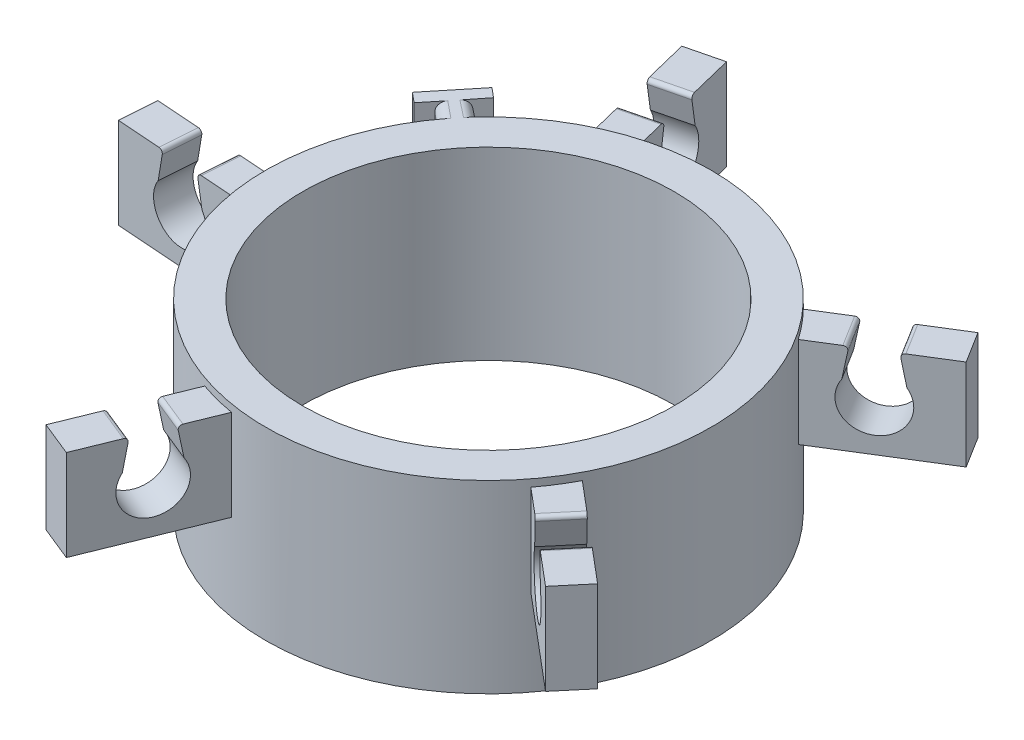
SolidWorks part; units mm, degrees
ref_plane "Plan de face" through (0, 0, 0) normal (0, 0, 1) x (1, 0, 0)
ref_plane "Plan de dessus" through (0, 0, 0) normal (0, 1, 0) x (1, 0, 0)
ref_plane "Plan de droite" through (0, 0, 0) normal (1, 0, 0) x (0, 0, -1)
sketch "Esquisse1" plane through (0, 0, 0) normal (0, 1, 0) x (1, 0, 0)
  circle A0 centre (0, 0) radius 10.05
  circle A1 centre (0, 0) radius 12.05
  dimension "D1" = 20.1
  dimension "D2" = 2
extrude "BASE" add sketch "Esquisse1" along normal blind 10
ref_axis "AXE BAGUE" through (0, 10, 0) along (0, -1, 0)
ref_plane "PLAN TUGE ASS" through (-2.524, 0, 0.6241) normal (0.9708, 0, -0.24) x (-0.24, 0, -0.9708)
ref_plane "Plan1" through (-2.524, 0, 0.6241) normal (0.9708, 0, -0.24) x (-0.24, 0, -0.9708)
sketch "Esquisse7" plane through (-2.524, 0, 0.6241) normal (0.9708, 0, -0.24) x (-0.24, 0, -0.9708)
  line L0 (15.0226, 7.1469) -> (15.0226, 9.9507) construction
  line L1 (11.4157, 9.6084) -> (18.6295, 9.6084)
  line L2 (11.4157, 9.6084) -> (11.4157, 4.6854)
  line L3 (11.4157, 4.6854) -> (18.6295, 4.6854)
  line L4 (18.6295, 9.6084) -> (18.6295, 4.6854)
  line L5 (11.4157, 9.6084) -> (18.6295, 4.6854) construction
  line L6 (11.4157, 4.6854) -> (18.6295, 9.6084) construction
  line L7 (16.3029, 8.0206) -> (16.0226, 9.6084)
  line L8 (13.7424, 8.0206) -> (14.0226, 9.6084)
  arc A2 (13.7424, 8.0206) -> (16.3029, 8.0206) centre (15.0226, 7.1469) ccw
  dimension "D1" = 3.1
  dimension "D2" = 4.923
  dimension "D3" = 1
  dimension "D4" = 1
extrude "BOSS TIGE" add sketch "Esquisse7" along normal blind 2 contours A2 L8 L1 L2 L3 L4 L7 region at (-5.5772, 9.5211, -11.7232)
fillet "CONGE TIGE" radius 0.2 2 edges at (-5.3994, 9.6084, -15.1701) (-4.9193, 9.6084, -13.2286)
pattern_circular "REP SUPPORT TIGE" count 5 over 360 about axis through (0, 10, 0) along (0, -1, 0) of "CONGE TIGE", "BOSS TIGE"
sketch "Esquisse8" plane through (0, 10, 0) normal (0, 1, 0) x (1, 0, 0)
  line L0 (-8.2684, 8.7574) -> (-7.7035, 8.3006)
  line L1 (-9.7984, 9.9904) -> (-11.7321, 7.6144)
  line L2 (-11.7321, 7.6144) -> (-11.1943, 7.1767)
  line L3 (-9.7984, 9.9904) -> (-9.6527, 5.922) construction
  line L4 (-7.7035, 8.3006) -> (-11.7321, 7.6144) construction
  line L5 (-9.7255, 7.9562) -> (-10.6924, 6.7682) construction
  line L6 (-10.6942, 7.7912) -> (-11.1943, 7.1767)
  line L7 (-10.6942, 7.7912) -> (-9.6903, 6.9741)
  line L8 (-9.6903, 6.9741) -> (-10.1904, 6.3597)
  line L9 (-9.7255, 7.9562) -> (-9.3234, 7.6339) construction
  line L10 (-9.7753, 8.9376) -> (-9.2844, 9.5595)
  line L11 (-8.7593, 8.1356) -> (-8.2684, 8.7574)
  line L12 (-9.7753, 8.9376) -> (-8.7593, 8.1356)
  line L13 (-10.1904, 6.3597) -> (-9.6527, 5.922)
  line L14 (-9.2844, 9.5595) -> (-9.7984, 9.9904)
  arc A0 (-7.7035, 8.3006) -> (-9.6527, 5.922) centre (0, 0) ccw
  circle A1 centre (0, 0) radius 12.05 construction
extrude "Boss.-Extru.1" add sketch "Esquisse8" against normal blind 3
fillet "Congé1" radius 0.5 4 edges at (-10.2354, 7, -7.4177) (-9.3048, 7, -8.5662) (-9.3048, 10, -8.5662) (-10.2354, 10, -7.4177)
